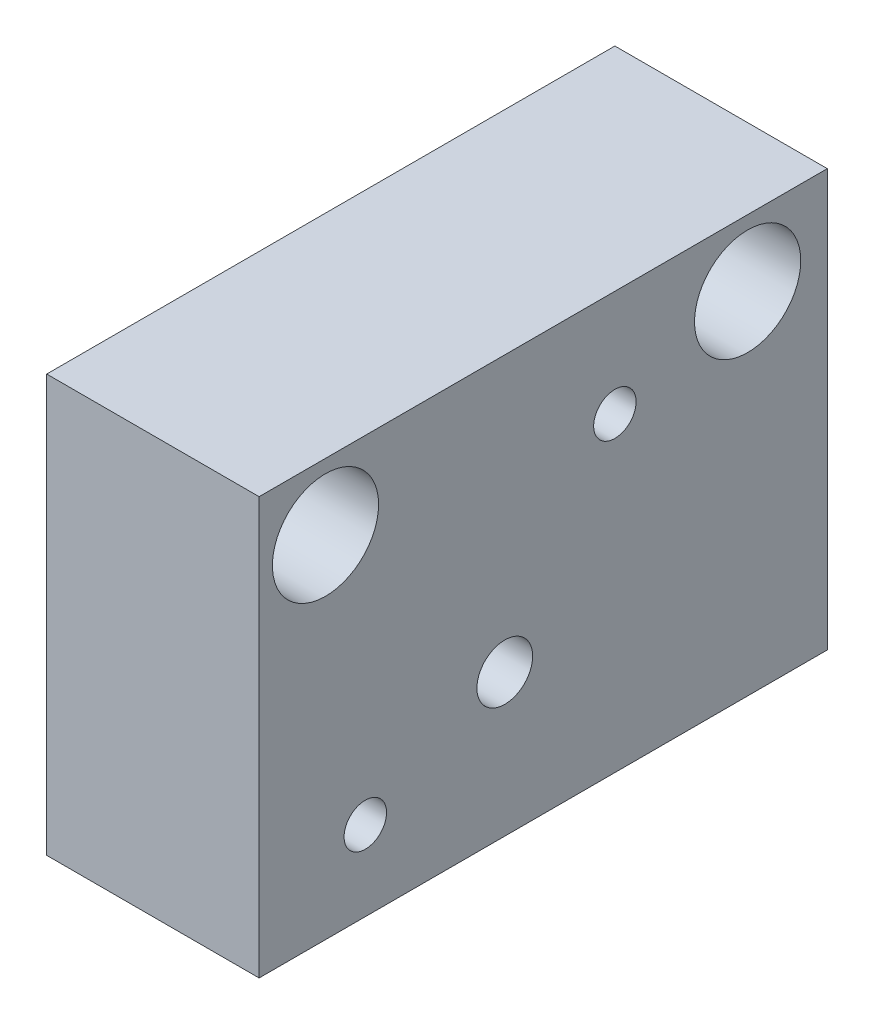
SolidWorks part; units mm, degrees
ref_plane "前视基准面" through (0, 0, 0) normal (0, 0, 1) x (1, 0, 0)
ref_plane "上视基准面" through (0, 0, 0) normal (0, 1, 0) x (1, 0, 0)
ref_plane "右视基准面" through (0, 0, 0) normal (1, 0, 0) x (0, 0, -1)
other "Configuration Table"
sketch "草图1" plane through (0, 0, 0) normal (0, 1, 0) x (1, 0, 0)
  line L33 (-4, -13.9) -> (4, -13.9)
  line L34 (-4, -13.9) -> (-4, 7.5)
  line L35 (-4, 7.5) -> (4, 7.5)
  line L36 (4, -13.9) -> (4, 7.5)
  line L37 (-4, -13.9) -> (4, 7.5) construction
  line L38 (-4, 7.5) -> (4, -13.9) construction
  circle A0 centre (0, 0) radius 2.6
  point P0 (-90.6464, 22.0667)
  point P9 (0, -3.2)
  dimension "D1" = 5.2
  dimension "D2" = 7.5
  dimension "D3" = 21.4
  dimension "D6" = 8
extrude "凸台-拉伸1" add sketch "草图1" along normal blind 15.7 contours L33 | L34 | L33 L36 L35 L34 region at (0, 0, 3.6532)
extrude "切除-拉伸1" cut sketch "草图1<18>" against normal blind 2.6 from surface contours A0 starting at face at (0, 15.7, 3.2)
sketch "草图1<18>" plane through (0, 0, 0) normal (0, 1, 0) x (1, 0, 0) same geometry as "草图1"
sketch "草图2" plane through (-4, 0, 0) normal (-1, 0, 0) x (0, 0, 1)
  circle A0 centre (4.6468, 10.3503) radius 1.05
  dimension "D1" = 2.1
extrude "切除-拉伸2" cut sketch "草图2" against normal through all contours A0
sketch "草图3" plane through (4, 0, 0) normal (1, 0, 0) x (0, 0, -1)
  circle A0 centre (4.5, 2.5) radius 2
  circle A1 centre (4.5, 2.5) radius 1.5
  circle A2 centre (-11.4, 2.5) radius 2
  circle A3 centre (-11.4, 2.5) radius 1.5
  dimension "D1" = 3
  dimension "D2" = 4
extrude "切除-拉伸4" cut sketch "草图3" against normal offset from surface (6 mm away) 2 contours A0 | A2 up to face at (-4, 10.3503, 5.6968)
extrude "切除-拉伸5" cut sketch "草图3<4>" against normal through all contours A3 | A1
sketch "草图3<4>" plane through (4, 0, 0) normal (1, 0, 0) x (0, 0, -1) same geometry as "草图3"
sketch "草图4" plane through (4, 0, 0) normal (1, 0, 0) x (0, 0, -1)
  line L0 (-13.9, 0) -> (7.5, 0) construction
  line L1 (-13.9, 15.7) -> (-13.9, 0) construction
  line L2 (-13.9, 15.7) -> (7.5, 15.7) construction
  line L3 (7.5, 15.7) -> (7.5, 0) construction
  circle A1 centre (-0.5, 4) radius 0.8
  circle A3 centre (-9.9, 12.7) radius 0.8
  dimension "D1" = 1.6
  dimension "D2" = 4
  dimension "D3" = 4
  dimension "D4" = 3
  dimension "D5" = 8
extrude "切除-拉伸6" cut sketch "草图4" against normal blind 4 contours A3 | A1
ref_plane "基准面1" through (0, -10, 0) normal (0, 1, 0) x (1, 0, 0)
mirror "镜向1" about plane through (0, -10, 0) normal (0, 1, 0) of bodies 191
sketch "草图5" plane through (0, -10, 0) normal (0, 1, 0) x (1, 0, 0)
  line L1 (-8.3508, 9.8639) -> (11.9377, 9.8639)
  line L2 (-8.3508, 9.8639) -> (-8.3508, -21.4345)
  line L3 (-8.3508, -21.4345) -> (11.9377, -21.4345)
  line L4 (11.9377, 9.8639) -> (11.9377, -21.4345)
extrude "切除-拉伸7" cut sketch "草图5" along normal through all
